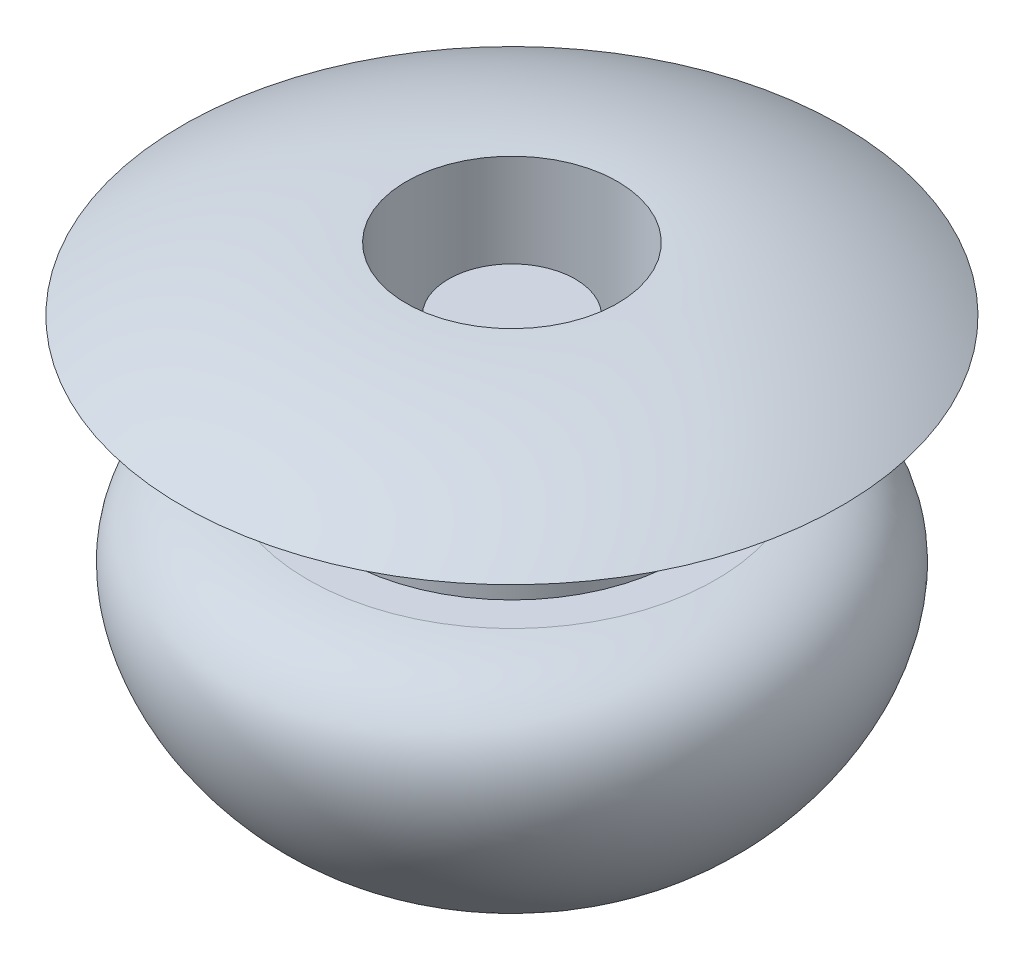
SolidWorks part; units mm, degrees
material "AISI 316 Stal nierdzewna odprężona (SS)"
ref_plane "Płaszczyzna przednia" through (0, 0, 0) normal (0, 0, 1) x (1, 0, 0)
ref_plane "Płaszczyzna górna" through (0, 0, 0) normal (0, 1, 0) x (1, 0, 0)
ref_plane "Płaszczyzna prawa" through (0, 0, 0) normal (1, 0, 0) x (0, 0, -1)
sketch "Szkic1" plane through (0, 0, 0) normal (1, 0, 0) x (0, 0, -1)
  line L1 (0, 0) -> (-0.75, 0)
  line L2 (-0.75, 0) -> (-0.75, -1.7007)
  line L3 (-0.75, -1.7007) -> (-1.25, -1.7007)
  line L4 (-1.25, -1.7007) -> (-1.25, 0.75)
  line L5 (-3.9, 0) -> (-2, 0)
  line L6 (-2, 0) -> (-2, -1.5)
  line L7 (-2, -1.5) -> (-2.4139, -1.5)
  line L8 (0, 0) -> (0, 0.4842) construction
  line L9 (0, -1.7007) -> (0, 0)
  line L10 (0, -1.7007) -> (0, -3.2007)
  line L11 (-10.4007, -1.5) -> (-6.4007, -1.5) construction
  arc A0 (-1.25, 0.75) -> (-3.9, 0) centre (-1.25, -4.3067) ccw
  ellipse E0 centre (0, -2.4507) end of major axis (-1.75, -2.4507) minor radius 0.75 (-0.956, -3.0789) -> (0, -3.2007) ccw
  spline S0 degree 3 poles (-2.4139, -1.5) (-3.8675, -1.6697) (-3.5289, -3.802) (-1.084, -5.3735) (-0.2718, -3.3749) (-0.956, -3.0789) knots 0 0 0 0 0.464993 0.721928 1 1 1 1
  dimension "D1" = 7.8
  dimension "D2" = 2.5
  dimension "D3" = 4
  dimension "D4" = 0.75
  dimension "D5" = 1.5
  dimension "D6" = 1.5
  dimension "D7" = 3.5
  dimension "D8" = 3.1855
  dimension "D9" = 2.5026
  dimension "D10" = 1.9
  dimension "D11" = 1.5789
  dimension "D12" = 0.5792
  dimension "D13" = 4.8278
  dimension "D14" = 3.3858
  dimension "D15" = 2.8395
  dimension "D16" = 1.25
  dimension "D17" = 0.6409
  dimension "D18" = 0.956
revolve "Obrót1" add sketch "Szkic1" angle 360 about L8
